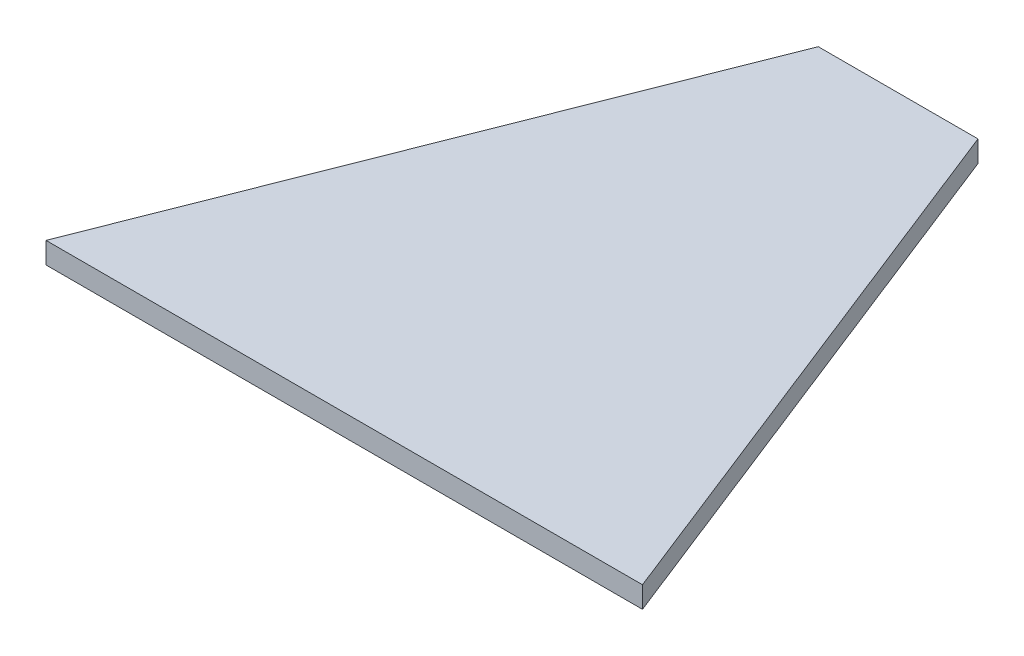
SolidWorks part; units mm, degrees
material "AISI 1020"
ref_plane "Спереди" through (0, 0, 0) normal (0, 0, 1) x (1, 0, 0)
ref_plane "Сверху" through (0, 0, 0) normal (0, 1, 0) x (1, 0, 0)
ref_plane "Справа" through (0, 0, 0) normal (1, 0, 0) x (0, 0, -1)
sketch "Эскиз1" plane through (0, 0, 0) normal (0, 1, 0) x (1, 0, 0)
  line L0 (-56, 0) -> (56, 0)
  line L1 (56, 0) -> (15, 104)
  line L2 (15, 1068) -> (15, 0) construction
  line L3 (15, 104) -> (-15, 104)
  line L4 (-15, 1068) -> (-15, 0) construction
  line L5 (-15, 104) -> (-56, 0)
  line L6 (-56, -10) -> (-56, -5) construction
  line L7 (56, -5) -> (56, -10) construction
  line L8 (-1013.4733, 104) -> (536.5267, 104) construction
base flange "Базовая кромка1" sketch "Эскиз1" thickness 4 reverse thickness direction yes parameters "D1"=0.74
sketch "Сгиб-Линии1" [suppressed] plane through (0, 0, 0) normal (0, 1, 0) x (1, 0, 0)
sketch "Граничная рамка1" [suppressed] plane through (0, 0, 0) normal (0, 1, 0) x (1, 0, 0)
sheet metal parameters "Листовой металл3" thickness 4 parameters "D1"=0.74
flat pattern "Развертка3" [suppressed]
sketch "Сгиб-Линии2" plane through (0, 0, 0) normal (0, 1, 0) x (1, 0, 0)
sketch3d "Граничная рамка2" [suppressed]
  line L0 (-56, 0, 0) -> (56, 0, 0) construction
  line L1 (-56, 104, 0) -> (56, 104, 0) construction
  line L2 (-56, 0, 0) -> (-56, 104, 0) construction
  line L3 (56, 0, 0) -> (56, 104, 0) construction
